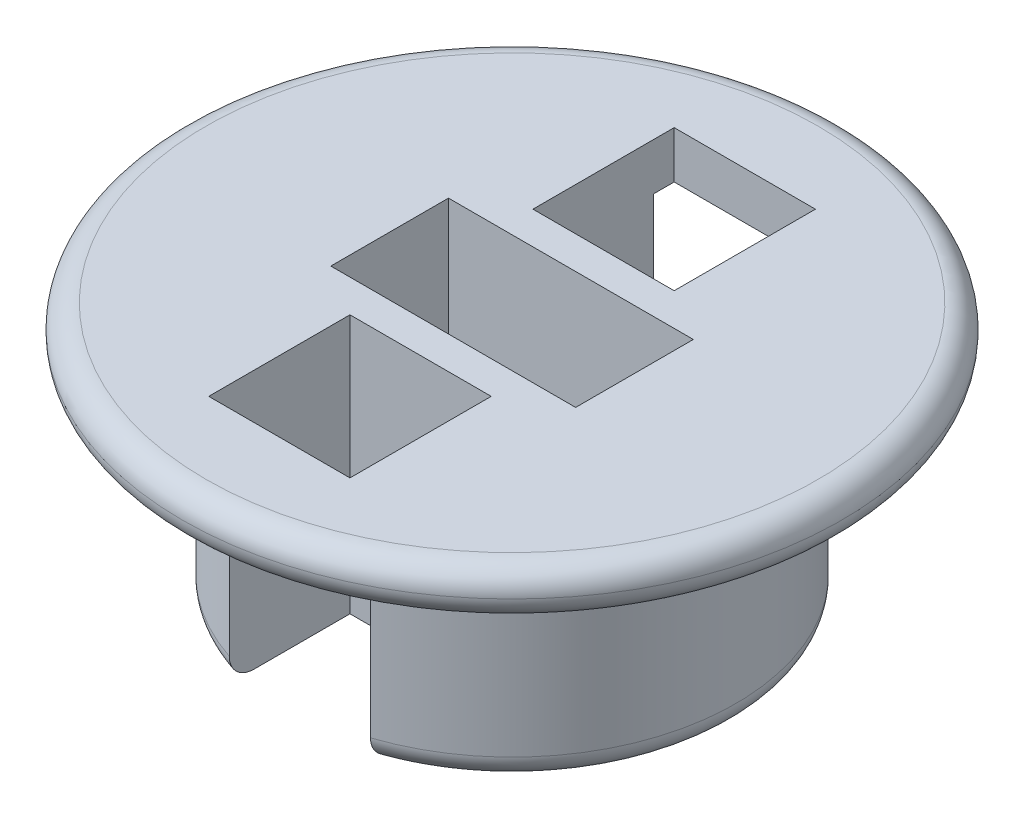
SolidWorks part; units mm, degrees
ref_plane "Front Plane" through (0, 0, 0) normal (0, 0, 1) x (1, 0, 0)
ref_plane "Top Plane" through (0, 0, 0) normal (0, 1, 0) x (1, 0, 0)
ref_plane "Right Plane" through (0, 0, 0) normal (1, 0, 0) x (0, 0, -1)
sketch "Sketch1" plane through (0, 0, 0) normal (0, 1, 0) x (1, 0, 0)
  circle A0 centre (0, 0) radius 4.75
extrude "Boss-Extrude1" add sketch "Sketch1" along normal blind 4.5 contours A0
sketch "Sketch2" plane through (0, 4.5, 0) normal (0, 1, 0) x (1, 0, 0)
  circle A0 centre (0, 0) radius 7
extrude "Boss-Extrude2" add sketch "Sketch2" along normal blind 1
sketch "Sketch3" plane through (0, 5.5, 0) normal (0, 1, 0) x (1, 0, 0)
  line L0 (0, -5.057) -> (0, 4.943) construction
  line L1 (0, -2.057) -> (0, 1.943) construction
  line L2 (-1.5, 4.943) -> (1.5, 4.943)
  line L3 (1.5, 4.943) -> (1.5, 1.943)
  line L4 (1.5, 1.943) -> (-1.5, 1.943)
  line L5 (-1.5, 1.943) -> (-1.5, 4.943)
  line L6 (-7, 0) -> (7, 0) construction
  line L7 (1.5, -1.943) -> (-1.5, -1.943)
  line L8 (-1.5, -1.943) -> (-1.5, -4.943)
  line L9 (1.5, -4.943) -> (1.5, -1.943)
  line L10 (-1.5, -4.943) -> (1.5, -4.943)
  circle A1 centre (0, 0) radius 7 construction
  point P4 (0, -0.057)
  point P7 (0, 0)
  point P11 (0, -0.057)
  point P13 (0, 4.943)
  point P21 (0, 0)
extrude "Cut-Extrude1" cut sketch "Sketch3" against normal through all contours L5 L2 L3 L4 | L8 L10 L9 L7
fillet "Fillet3" radius 0.5 4 edges at (4.75, 0, 0) (-4.75, 0, 0) (0, 4.5, 7) (0, 5.5, 7)
sketch "Sketch4" plane through (0, 5.5, 0) normal (0, 1, 0) x (1, 0, 0)
  line L0 (-2.6, 0) -> (2.6, 0) construction
  line L1 (0, -1.25) -> (0, 1.25) construction
  line L2 (-2.6, 1.25) -> (2.6, 1.25)
  line L3 (2.6, 1.25) -> (2.6, -1.25)
  line L4 (2.6, -1.25) -> (-2.6, -1.25)
  line L5 (-2.6, -1.25) -> (-2.6, 1.25)
  point P5 (0, 0)
  point P9 (0, 0)
extrude "Cut-Extrude2" cut sketch "Sketch4" against normal through all
